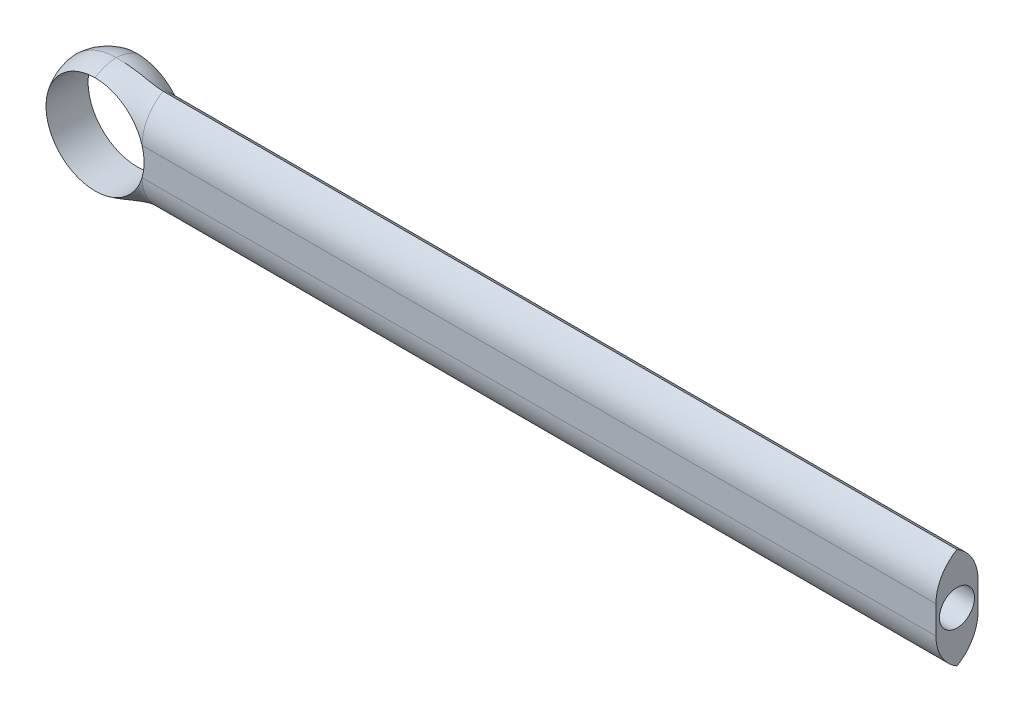
SolidWorks part; units mm, degrees
ref_plane "Ön Düzlem" through (0, 0, 0) normal (0, 0, 1) x (1, 0, 0)
ref_plane "Üst Düzlem" through (0, 0, 0) normal (0, 1, 0) x (1, 0, 0)
ref_plane "Sağ Düzlem" through (0, 0, 0) normal (1, 0, 0) x (0, 0, -1)
sketch "Çizim1" plane through (0, 0, 0) normal (0, 0, 1) x (1, 0, 0)
  line L0 (0, 4) -> (60, 4)
  line L1 (0, -4) -> (60, -4)
  line L2 (60, 4) -> (60, -4)
  circle A0 centre (0, 0) radius 3.5
  circle A1 centre (0, 0) radius 4
  dimension "D1" = 7
  dimension "D2" = 8
  dimension "D3" = 60
  dimension "D4" = 60
extrude "Yükseklik-Ekstrüzyon1" add sketch "Çizim1" along normal blind 3 contours A1 A0 | A1 L1 L2 L0 region at (31.5638, 0, 0) region at (2.7484, 2.7484, 0)
sketch "Çizim2" plane through (60, 0, 0) normal (1, 0, 0) x (0, 0, -1)
  line L0 (-1.5, 4) -> (-1.5, -4) construction
  line L1 (-3, 4) -> (0, 4) construction
  line L2 (-3, -4) -> (0, -4) construction
  circle A0 centre (-1.5, 0) radius 1.25
  dimension "D1" = 2.5
extrude "Kes-Ekstrüzyon1" cut sketch "Çizim2" against normal blind 50
fillet "Radyus1" radius 3 4 edges at (30, -4, 3) (30, -4, 0) (30, 4, 3) (30, 4, 0)
